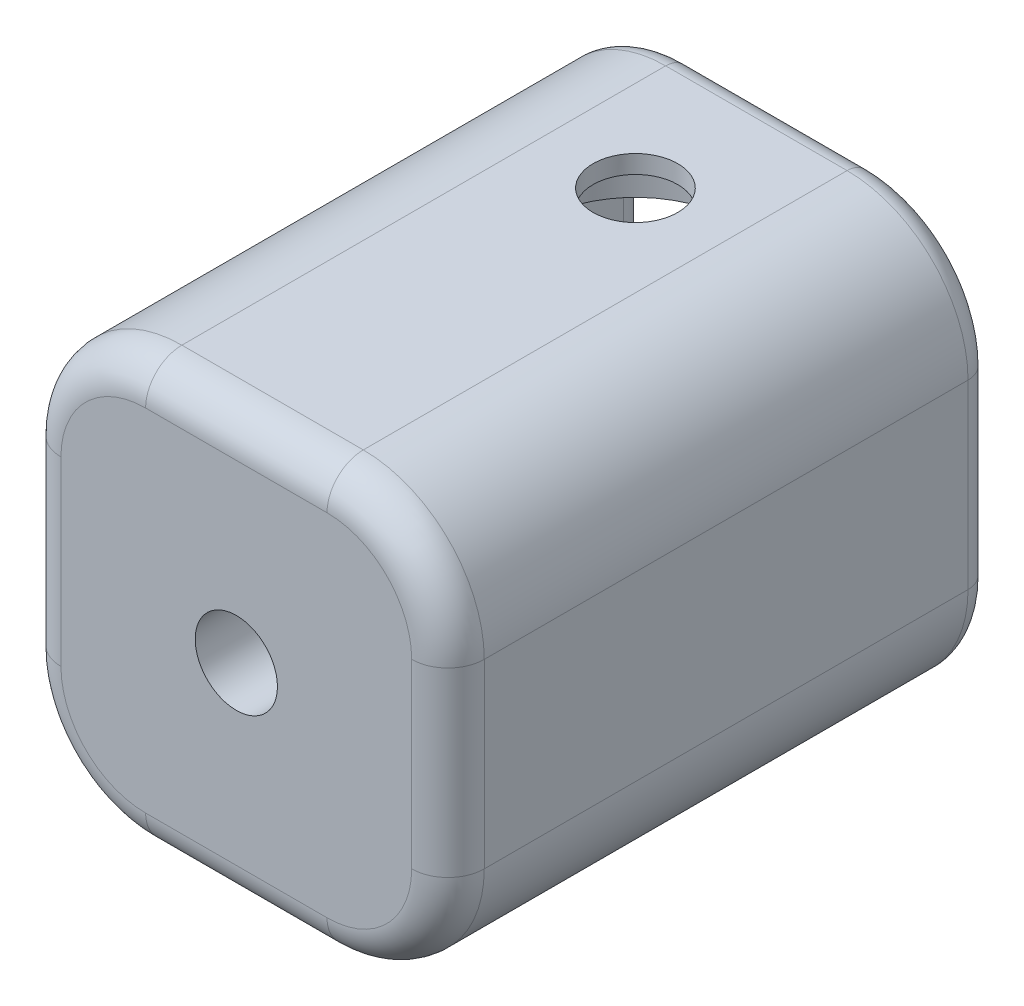
SolidWorks part; units mm, degrees
ref_plane "Front Plane" through (0, 0, 0) normal (0, 0, 1) x (1, 0, 0)
ref_plane "Top Plane" through (0, 0, 0) normal (0, 1, 0) x (1, 0, 0)
ref_plane "Right Plane" through (0, 0, 0) normal (1, 0, 0) x (0, 0, -1)
sketch "Sketch1" plane through (0, 0, 0) normal (0, 0, 1) x (1, 0, 0)
  line L1 (-11, 11) -> (11, 11)
  line L2 (-11, 11) -> (-11, -11)
  line L3 (-11, -11) -> (11, -11)
  line L4 (11, 11) -> (11, -11)
  line L5 (-11, 11) -> (11, -11) construction
  line L6 (-11, -11) -> (11, 11) construction
  line L7 (-17.5, 17.5) -> (17.5, 17.5)
  line L8 (-17.5, 17.5) -> (-17.5, -17.5)
  line L9 (-17.5, -17.5) -> (17.5, -17.5)
  line L10 (17.5, 17.5) -> (17.5, -17.5)
  line L11 (-17.5, 17.5) -> (17.5, -17.5) construction
  line L12 (-17.5, -17.5) -> (17.5, 17.5) construction
  point P0 (0, 0)
  point P6 (0, 0)
  dimension "D1" = 22
  dimension "D2" = 22
  dimension "D3" = 35
  dimension "D4" = 35
extrude "Boss-Extrude1" add sketch "Sketch1" along normal blind 30
ref_plane "Plane1" through (0, 0, 0) normal (0, 1, 0) x (1, 0, 0)
sketch "Sketch3" plane through (0, 17.5, 0) normal (0, 1, 0) x (1, 0, 0)
  line L0 (0, 0) -> (0, -30) construction
  line L1 (17.5, 0) -> (-17.5, 0) construction
  line L2 (17.5, -30) -> (-17.5, -30) construction
  circle A0 centre (0, -12) radius 3.5
  dimension "D1" = 7
  dimension "D2" = 12
extrude "Cut-Extrude2" cut sketch "Sketch3" against normal through all
sketch "Sketch4" plane through (0, -11, 0) normal (0, 1, 0) x (1, 0, 0)
  circle A0 centre (0, -12) radius 8.25
  dimension "D1" = 16.5
extrude "Cut-Extrude3" cut sketch "Sketch4" against normal blind 5
mirror "Mirror2" about plane through (0, 0, 0) normal (0, 1, 0) of "Cut-Extrude3"
fillet "Fillet1" radius 10 4 edges at (17.5, 17.5, 15) (17.5, -17.5, 15) (-17.5, -17.5, 15) (-17.5, 17.5, 15)
fillet "Fillet4" radius 2 8 edges at (14.5711, 14.5711, 0) (17.5, 0, 0) (14.5711, -14.5711, 0) (0, -17.5, 0) (-14.5711, -14.5711, 0) (-17.5, 0, 0) (-14.5711, 14.5711, 0) (0, 17.5, 0)
fillet "Fillet5" radius 3 4 edges at (-11, 11, 15) (11, 11, 15) (11, -11, 15) (-11, -11, 15)
sketch "Sketch6" plane through (0, 0, 30) normal (0, 0, 1) x (1, 0, 0)
  line L1 (7.5, 17.5) -> (-7.5, 17.5)
  line L2 (17.5, 7.5) -> (17.5, -7.5)
  line L3 (7.5, -17.5) -> (-7.5, -17.5)
  line L4 (-17.5, 7.5) -> (-17.5, -7.5)
  line L5 (17.5, 17.5) -> (-17.5, -17.5) construction
  line L6 (17.5, -17.5) -> (-17.5, 17.5) construction
  arc A0 (-7.5, -17.5) -> (-17.5, -7.5) centre (-7.5, -7.5) cw
  arc A1 (17.5, -7.5) -> (7.5, -17.5) centre (7.5, -7.5) cw
  arc A2 (7.5, 17.5) -> (17.5, 7.5) centre (7.5, 7.5) cw
  arc A3 (-7.5, 17.5) -> (-17.5, 7.5) centre (-7.5, 7.5) ccw
  point P0 (0, 0)
  dimension "D3" = 10
  dimension "D1" = 35
  dimension "D2" = 35
extrude "Nut Retention Area" add sketch "Sketch6" along normal blind 15
sketch "Sketch7" plane through (0, 0, 45) normal (0, 0, 1) x (1, 0, 0)
  circle A0 centre (0, 0) radius 3.4
  dimension "D1" = 6.8
sketch "Sketch8" plane through (0, 0, 30) normal (0, 0, -1) x (-1, 0, 0)
  line L1 (3.2332, -5.6) -> (6.4663, 0)
  line L2 (6.4663, 0) -> (3.2332, 5.6)
  line L3 (3.2332, 5.6) -> (-3.2332, 5.6)
  line L4 (-3.2332, 5.6) -> (-6.4663, 0)
  line L5 (-6.4663, 0) -> (-3.2332, -5.6)
  line L6 (-3.2332, -5.6) -> (3.2332, -5.6)
  circle A0 centre (0, 0) radius 5.6 construction
  dimension "D1" = 11.2
extrude "Cut-Extrude5" cut sketch "Sketch8" against normal blind 8 contours L3 L4 L5 L6 L1 L2
sketch "Sketch9" plane through (0, 0, 30) normal (0, 0, -1) x (-1, 0, 0)
  circle A0 centre (0, 0) radius 8.5
  dimension "D1" = 17
extrude "Nut Captivator" [suppressed] add sketch "Sketch9" against normal blind 2.3 contours A0
extrude "Cut-Extrude6" cut sketch "Sketch7" against normal through all contours A0
fillet "Fillet6" radius 3 8 edges at (0, 17.5, 45) (14.5711, 14.5711, 45) (17.5, 0, 45) (14.5711, -14.5711, 45) (0, -17.5, 45) (-14.5711, -14.5711, 45) (-17.5, 0, 45) (-14.5711, 14.5711, 45)
fillet "Fillet7" radius 2 8 edges at (10.1213, 10.1213, 0) (11, 0, 0) (10.1213, -10.1213, 0) (0, -11, 0) (-10.1213, -10.1213, 0) (-11, 0, 0) (-10.1213, 10.1213, 0) (0, 11, 0)
equation "\"Core_Height\" = 35"
equation "\"D3@Sketch1\"=\"Core_Height\""
